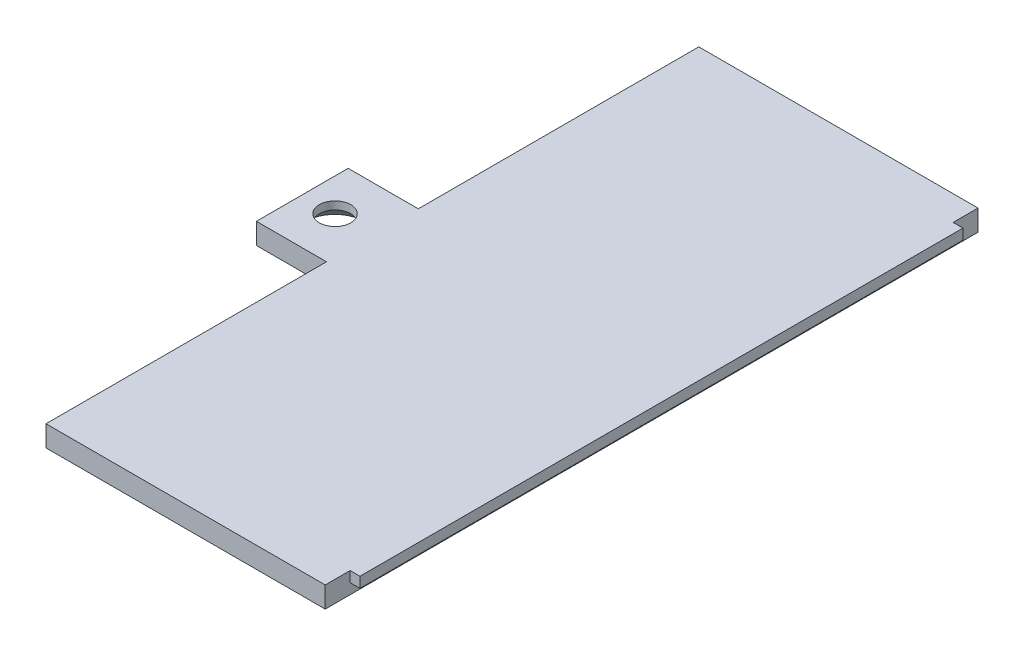
SolidWorks part; units mm, degrees
ref_plane "Front Plane" through (0, 0, 0) normal (0, 0, 1) x (1, 0, 0)
ref_plane "Top Plane" through (0, 0, 0) normal (0, 1, 0) x (1, 0, 0)
ref_plane "Right Plane" through (0, 0, 0) normal (1, 0, 0) x (0, 0, -1)
sketch "Door Plate 1.6 + centred screw tab Sketch" plane through (0, 0, 0) normal (0, 1, 0) x (1, 0, 0)
  line L0 (9.35, 15.1) -> (30.65, 15.1)
  line L1 (30.65, 15.1) -> (30.65, 64.9)
  line L2 (30.65, 64.9) -> (9.35, 64.9)
  line L3 (9.35, 64.9) -> (9.35, 43.5)
  line L4 (9.35, 43.5) -> (4, 43.5)
  line L5 (4, 43.5) -> (4, 36.5)
  line L6 (4, 36.5) -> (9.35, 36.5)
  line L7 (9.35, 36.5) -> (9.35, 15.1)
extrude "Door Plate 1.6 + centred screw tab" add sketch "Door Plate 1.6 + centred screw tab Sketch" along normal blind 1.6
ref_plane "Hook Tongue Plane d17" through (0, 0, -17) normal (0, 0, 1) x (1, 0, 0)
sketch "Screw Hole 2.4 (free) Sketch" plane through (0, 0, 0) normal (0, 1, 0) x (1, 0, 0)
  circle A0 centre (6.5, 40) radius 1.2
extrude "Screw Hole 2.4 (free)" cut sketch "Screw Hole 2.4 (free) Sketch" along normal through all
chamfer "Screw CSK 90deg (M2)" distance 1 angle 45 1 edges at (6.5, 0, -38.8)
ref_plane "Hook Flange Plane y0.8" through (0, 0.8, 0) normal (0, 1, 0) x (1, 0, 0)
sketch "Hook Flange 0.75 x 0.8 (inner-face plane) Sketch" plane through (0, 0.8, 0) normal (0, 1, 0) x (1, 0, 0)
  line L0 (30.5, 17) -> (31.4, 17)
  line L1 (31.4, 17) -> (31.4, 63)
  line L2 (31.4, 63) -> (30.5, 63)
  line L3 (30.5, 63) -> (30.5, 17)
extrude "Hook Flange 0.75 x 0.8 (inner-face plane)" add sketch "Hook Flange 0.75 x 0.8 (inner-face plane) Sketch" along normal blind 0.8
